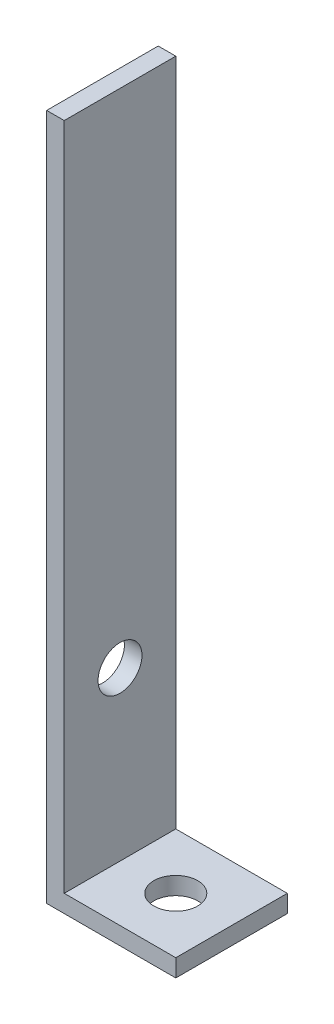
SolidWorks part; units mm, degrees
ref_plane "Front Plane" through (0, 0, 0) normal (0, 0, 1) x (1, 0, 0)
ref_plane "Top Plane" through (0, 0, 0) normal (0, 1, 0) x (1, 0, 0)
ref_plane "Right Plane" through (0, 0, 0) normal (1, 0, 0) x (0, 0, -1)
sketch "Sketch1" plane through (0, 0, 0) normal (0, 0, 1) x (1, 0, 0)
  line L1 (0, 0) -> (14.7, 0)
  line L2 (0, 0) -> (0, 2)
  line L3 (0, 2) -> (14.7, 2)
  line L4 (14.7, 0) -> (14.7, 2)
  line L5 (0, 2) -> (2, 2)
  line L6 (0, 2) -> (0, 78.2)
  line L7 (0, 78.2) -> (2, 78.2)
  line L8 (2, 2) -> (2, 78.2)
  dimension "D1" = 2
  dimension "D2" = 12.7
  dimension "D3" = 76.2
extrude "Boss-Extrude1" add sketch "Sketch1" along normal blind 12.7 contours L1 L4 L3 L2 | L6 L5 L8 L7 region at (7.35, 1, 0)
hole_wizard "Ø5.0mm Dowel Hole1" positions "Sketch2" profile "Sketch3" hole size "Ø5.0" standard "ANSI Metric" end condition through all
sketch "Sketch2" plane through (2, 0, 0) normal (1, 0, 0) x (0, 0, -1)
  line L0 (-12.7, 78.2) -> (0, 78.2) construction
  line L1 (-12.7, 2) -> (0, 2) construction
  point P0 (-6.35, 21.05)
  point P5 (-6.35, 78.2)
  dimension "D1" = 19.05
sketch "Sketch3" plane through (2, 21.05, 6.35) normal (0, 1, 0) x (0, 0, -1)
  line L0 (0, 0) -> (0, 2)
  line L1 (0, 2) -> (2.5, 2)
  line L2 (2.5, 2) -> (2.5, 0)
  line L5 (2.5, 0) -> (0, 0)
  line L11 (0, -6.35) -> (0, 107.95) construction
  dimension "Thru Hole Dia." = 5
  dimension "Thru Hole Depth" = 2
hole_wizard "Ø5.0mm Dowel Hole2" positions "Sketch4" profile "Sketch5" hole size "Ø5.0" standard "ANSI Metric" end condition through all
sketch "Sketch4" plane through (0, 2, 0) normal (0, 1, 0) x (1, 0, 0)
  line L0 (2, -12.7) -> (14.7, -12.7) construction
  line L1 (14.7, -12.7) -> (14.7, 0) construction
  point P0 (8.35, -6.35)
  point P5 (8.35, -12.7)
  point P8 (14.7, -6.35)
sketch "Sketch5" plane through (8.35, 2, 6.35) normal (1, 0, 0) x (0, 0, 1)
  line L0 (0, 0) -> (0, 2)
  line L1 (0, 2) -> (2.5, 2)
  line L2 (2.5, 2) -> (2.5, 0)
  line L5 (2.5, 0) -> (0, 0)
  line L11 (0, -6.35) -> (0, 107.95) construction
  dimension "Thru Hole Dia." = 5
  dimension "Thru Hole Depth" = 2
